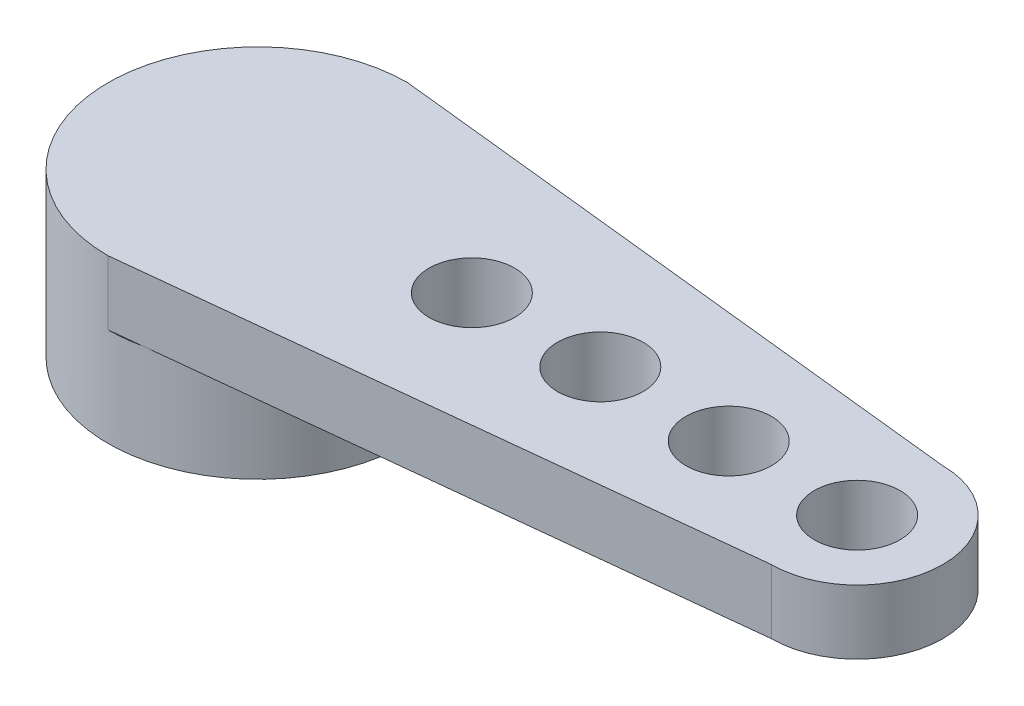
SolidWorks part; units mm, degrees
ref_plane "Front Plane" through (0, 0, 0) normal (0, 0, 1) x (1, 0, 0)
ref_plane "Top Plane" through (0, 0, 0) normal (0, 1, 0) x (1, 0, 0)
ref_plane "Right Plane" through (0, 0, 0) normal (1, 0, 0) x (0, 0, -1)
sketch "Sketch1" plane through (0, 0, 0) normal (0, 1, 0) x (1, 0, 0)
  line L0 (0, 0) -> (14, 0) construction
  line L1 (0, 3.5) -> (14, 2)
  line L2 (0, -3.5) -> (14, -2)
  arc A0 (0, 3.5) -> (0, -3.5) centre (0, 0) ccw
  arc A1 (14, -2) -> (14, 2) centre (14, 0) ccw
  point P4 (0, 0)
  point P10 (0.7415, 3.4206)
  point P11 (0.7415, 3.4206)
  dimension "D1" = 7
  dimension "D2" = 4
  dimension "D3" = 14
extrude "Boss-Extrude1" add sketch "Sketch1" along normal blind 1.5
sketch "Sketch2" plane through (0, 0, 0) normal (0, -1, 0) x (1, 0, 0)
  circle A0 centre (0, 0) radius 2.4
  circle A1 centre (0, 0) radius 3.5
  dimension "D1" = 7
  dimension "D2" = 4.8
extrude "Boss-Extrude2" add sketch "Sketch2" along normal blind 2.3
sketch "Sketch3" plane through (0, 1.5, 0) normal (0, 1, 0) x (1, 0, 0)
  line L0 (0, 0) -> (16, 0) construction
  arc A1 (14, -2) -> (14, 2) centre (14, 0) ccw construction
  circle A2 centre (14, 0) radius 1
  circle A8 centre (11, 0) radius 1
  circle A9 centre (8, 0) radius 1
  circle A10 centre (5, 0) radius 1
  dimension "D1" = 2
  dimension "D2" = 2
  dimension "D3" = 4
extrude "Cut-Extrude2" cut sketch "Sketch3" against normal through all
